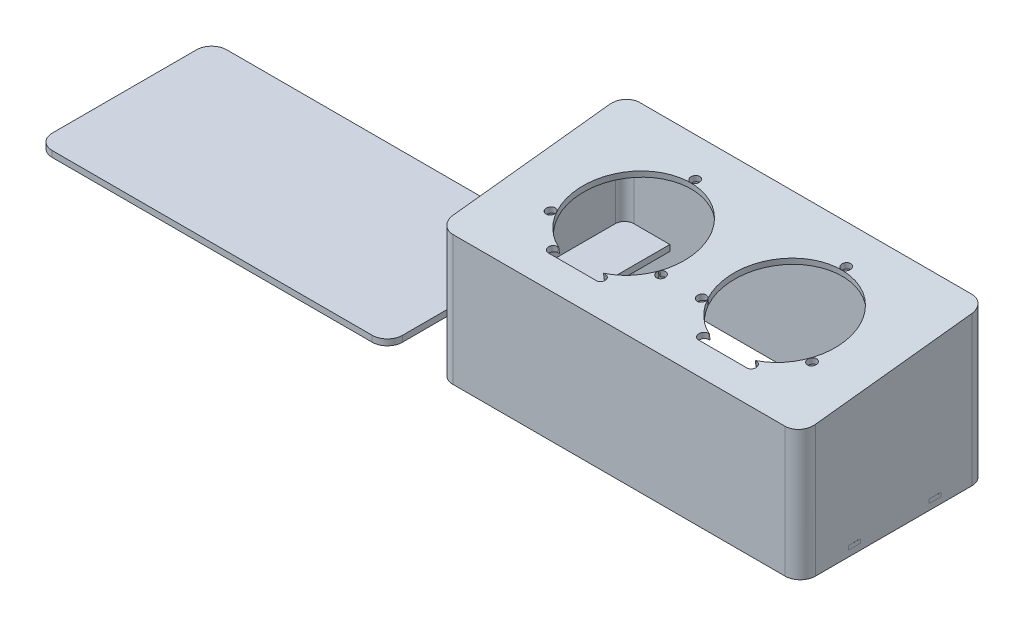
SolidWorks part; units mm, degrees
other "标注1"
sketch "草图11" plane through (-40.2583, 0, -30.485) normal (-0.2386, -0.9638, -0.1194) x (0.9603, -0.2525, 0.1189)
other "标注2"
sketch "草图19" plane through (79.7417, 0, 31.315) normal (0.7607, -0.6049, 0.2355) x (-0.4746, -0.2707, 0.8375)
other "标注3"
sketch "草图27" plane through (-40.2583, 0, -30.485) normal (-0.024, -0.9264, -0.3759) x (0.9235, 0.1235, -0.3633)
ref_plane "前视基准面" through (0, 0, 0) normal (0, 0, 1) x (1, 0, 0)
ref_plane "上视基准面" through (0, 0, 0) normal (0, 1, 0) x (1, 0, 0)
ref_plane "右视基准面" through (0, 0, 0) normal (1, 0, 0) x (0, 0, -1)
other "Configuration Table"
sketch "草图3" plane through (0, 0, 0) normal (0, 1, 0) x (1, 0, 0)
  line L1 (-35.2583, 30.485) -> (74.7417, 30.485)
  line L2 (-40.2583, 25.485) -> (-40.2583, -26.315)
  line L3 (-35.2583, -31.315) -> (74.7417, -31.315)
  line L4 (79.7417, 25.485) -> (79.7417, -26.315)
  arc A0 (-40.2583, -26.315) -> (-35.2583, -31.315) centre (-35.2583, -26.315) ccw
  arc A1 (74.7417, -31.315) -> (79.7417, -26.315) centre (74.7417, -26.315) ccw
  arc A2 (74.7417, 30.485) -> (79.7417, 25.485) centre (74.7417, 25.485) cw
  arc A3 (-35.2583, 30.485) -> (-40.2583, 25.485) centre (-35.2583, 25.485) ccw
  point P6 (-40.2583, -31.315)
  point P11 (79.7417, 30.485)
  point P14 (-40.2583, 30.485)
  dimension "D3" = 5
  dimension "D1" = 61.8
  dimension "D2" = 120
extrude "凸台-拉伸6" add sketch "草图3" along normal blind 50 contours A3 L2 A0 L3 A1 L4 A2 L1
sketch "草图4" plane through (79.7417, 0, 0) normal (1, 0, 0) x (0, 0, -1)
  line L0 (30.485, 50) -> (-31.315, 43)
  line L1 (-31.315, 50) -> (-31.315, 0) construction
  line L2 (-31.315, 43) -> (-31.315, 50)
  line L3 (-31.315, 50) -> (30.485, 50)
  dimension "D1" = 7
extrude "切除-拉伸1" cut sketch "草图4" against normal through all both and the other way through all contours L3 L0 L2
sketch "草图5" plane through (0, 45.9574, 5.2055) normal (0, 0.9936, 0.1125) x (1, 0, 0)
  line L0 (19.7417, -26.2764) -> (19.7417, 35.9188) construction
  line L1 (-35.2583, -26.2764) -> (74.7417, -26.2764) construction
  line L2 (-35.2583, 35.9188) -> (74.7417, 35.9188) construction
  circle A0 centre (44.7417, 3.7236) radius 19
  circle A1 centre (-5.2583, 3.7236) radius 19
  dimension "D1" = 50
  dimension "D2" = 30
extrude "切除-拉伸2" cut sketch "草图5" against normal through all contours A1 | A0
sketch "草图7" plane through (0, 0, 0) normal (0, -1, 0) x (-1, 0, 0)
  line L0 (168.7524, -30.5948) -> (62.7524, -30.5948)
  line L1 (33.2583, -29.315) -> (-72.7417, -29.315)
  line L2 (38.2583, -24.315) -> (38.2583, 23.485)
  line L3 (33.2583, 28.485) -> (-72.7417, 28.485)
  line L4 (-77.7417, -24.315) -> (-77.7417, 23.485)
  line L5 (35.2583, -31.315) -> (-74.7417, -31.315) construction
  line L6 (35.2583, 30.485) -> (-74.7417, 30.485) construction
  line L7 (40.2583, 25.485) -> (40.2583, -26.315) construction
  line L8 (-79.7417, 25.485) -> (-79.7417, -26.315) construction
  line L9 (173.7524, -25.5948) -> (173.7524, 22.2052)
  line L10 (168.7524, 27.2052) -> (62.7524, 27.2052)
  line L11 (57.7524, -25.5948) -> (57.7524, 22.2052)
  arc A0 (173.7524, 22.2052) -> (168.7524, 27.2052) centre (168.7524, 22.2052) ccw
  arc A1 (38.2583, 23.485) -> (33.2583, 28.485) centre (33.2583, 23.485) ccw
  arc A2 (-72.7417, 28.485) -> (-77.7417, 23.485) centre (-72.7417, 23.485) ccw
  arc A3 (-72.7417, -29.315) -> (-77.7417, -24.315) centre (-72.7417, -24.315) cw
  arc A4 (33.2583, -29.315) -> (38.2583, -24.315) centre (33.2583, -24.315) ccw
  arc A5 (62.7524, 27.2052) -> (57.7524, 22.2052) centre (62.7524, 22.2052) ccw
  arc A6 (62.7524, -30.5948) -> (57.7524, -25.5948) centre (62.7524, -25.5948) cw
  arc A7 (168.7524, -30.5948) -> (173.7524, -25.5948) centre (168.7524, -25.5948) ccw
  point P14 (38.2583, 28.485)
  point P19 (-77.7417, -29.315)
  point P22 (38.2583, -29.315)
  dimension "D7" = 5
  dimension "D1" = 116
  dimension "D2" = 57.8
  dimension "D3" = 2
  dimension "D4" = 2
  dimension "D5" = 2
  dimension "D6" = 2
shell "抽壳3" thickness 1.9179 removed face at (44.7417, 0, 15.3741) removed face at (-5.2583, 0, 15.3741) removed face at (-5.2583, 0, 15.3741)
sketch "草图10" plane through (0, 44.0516, 4.9897) normal (0, -0.9936, -0.1125) x (1, 0, 0)
  circle A0 centre (-5.2583, -3.7236) radius 22
  circle A1 centre (-5.2583, -3.7236) radius 19 construction
  circle A2 centre (44.7417, -3.7236) radius 22
  circle A3 centre (44.7417, -3.7236) radius 19 construction
sketch "草图15" plane through (77.8238, 0, 0) normal (-1, 0, 0) x (0, 0, 1)
  line L0 (0, 20) -> (-28.5671, 20)
  line L1 (0, 18) -> (0, 0)
  line L2 (-28.5671, 47.8525) -> (-28.5671, 0) construction
  line L3 (0, 18) -> (-28.5671, 18)
  line L6 (-28.5671, 18) -> (-28.5671, 20)
  line L11 (29.397, 41.287) -> (29.397, 0) construction
  line L12 (0, 18) -> (29.397, 18)
  line L14 (0, 20) -> (29.397, 20)
  line L15 (29.397, 18) -> (29.397, 20)
  line L19 (26.315, 41.6361) -> (-25.485, 47.5034)
  line L20 (26.315, 0) -> (26.315, 41.6361)
  line L21 (-25.485, 0) -> (26.315, 0)
  line L22 (-25.485, 47.5034) -> (-25.485, 0)
  line L23 (26.315, 41.6361) -> (-25.485, 47.5034)
  line L24 (26.315, 0) -> (26.315, 41.6361)
  line L25 (-25.485, 0) -> (26.315, 0)
  line L26 (-25.485, 47.5034) -> (-25.485, 0)
  dimension "D1" = 0
sketch "草图17" plane through (0, 45.9574, 5.2055) normal (0, 0.9936, 0.1125) x (1, 0, 0)
sketch "草图18" plane through (0, 45.9574, 5.2055) normal (0, 0.9936, 0.1125) x (1, 0, 0)
  line L0 (-13.2107, -15.2764) -> (2.7893, -15.2764) construction
  line L1 (-13.2107, -13.7764) -> (2.7893, -13.7764)
  line L2 (-13.2107, -16.7764) -> (2.7893, -16.7764)
  line L3 (36.7178, -15.2764) -> (52.7178, -15.2764) construction
  line L4 (36.7178, -13.6873) -> (52.7178, -13.6873)
  line L5 (36.7178, -16.8655) -> (52.7178, -16.8655)
  arc A0 (-13.2107, -13.7764) -> (-13.2107, -16.7764) centre (-13.2107, -15.2764) ccw
  arc A1 (2.7893, -16.7764) -> (2.7893, -13.7764) centre (2.7893, -15.2764) ccw
  circle A2 centre (-5.2583, 3.7236) radius 19 construction
  arc A3 (36.7178, -13.6873) -> (36.7178, -16.8655) centre (36.7178, -15.2764) ccw
  arc A4 (52.7178, -16.8655) -> (52.7178, -13.6873) centre (52.7178, -15.2764) ccw
  circle A6 centre (44.7417, 3.7236) radius 19 construction
  point P2 (-5.2107, -15.2764)
  point P11 (44.7178, -15.2764)
extrude "切除-拉伸3" cut sketch "草图18" against normal blind 20
sketch "草图20" plane through (0, 45.9574, 5.2055) normal (0, 0.9936, 0.1125) x (1, 0, 0)
  line L0 (19.7417, -26.2764) -> (19.7417, 28.304)
  line L1 (-35.2583, -26.2764) -> (74.7417, -26.2764) construction
  line L2 (-33.2583, 28.304) -> (72.7417, 28.304) construction
  line L3 (-23.5613, -5.5563) -> (-38.2583, -5.5563) construction
  line L4 (-38.2583, -24.1605) -> (-38.2583, 23.3358) construction
  line L5 (-38.2583, -5.5563) -> (77.7417, -5.5563)
  line L6 (77.7417, -24.1605) -> (77.7417, 23.3358) construction
  line L7 (-5.2583, 3.7236) -> (-5.2583, -5.5563)
  line L8 (-5.2583, -5.5563) -> (-5.2583, 28.304)
  circle A5 centre (-5.2617, 24.2356) radius 1.5
  circle A6 centre (-23.5613, -5.5563) radius 1.5
  circle A7 centre (63.0448, -5.5563) radius 1.5
  circle A8 centre (13.0194, -5.5392) radius 1.5
  circle A9 centre (26.464, -5.5392) radius 1.5
  circle A10 centre (44.7451, 24.2356) radius 1.5
extrude "切除-拉伸4" cut sketch "草图20" against normal blind 20 contours A7 | A8 | A6 | A10 | A9 | A5
sketch "草图22" plane through (79.7417, 0, 0) normal (1, 0, 0) x (0, 0, -1)
sketch "草图24" plane through (79.7417, 0, 0) normal (1, 0, 0) x (0, 0, -1)
extrude "凸台-拉伸10" add sketch "草图15" along normal blind 21 contours L6 L0 L14 L15 L12 L3
sketch "草图25" plane through (-40.2583, 0, 0) normal (-1, 0, 0) x (0, 0, 1)
  line L1 (-30.485, 50) -> (-30.485, 0) construction
  line L3 (-30.485, 20) -> (-30.485, 18)
  point P0 (0, 0)
sketch "草图26" plane through (-38.3403, 0, 0) normal (1, 0, 0) x (0, 0, -1)
  line L3 (-29.0671, 16.1759) -> (28.897, 16.1759)
  line L4 (-29.0671, 16.1759) -> (-29.0671, 14.1759)
  line L5 (-29.0671, 14.1759) -> (28.897, 14.1759)
  line L6 (28.897, 16.1759) -> (28.897, 14.1759)
  point P9 (0, 0)
extrude "凸台-拉伸11" add sketch "草图26" along normal blind 15 contours L5 L6 L3 L4
sketch "草图28" plane through (0, 44.0516, 4.9897) normal (0, -0.9936, -0.1125) x (1, 0, 0)
  arc A0 (-21.0475, 22.378) -> (-22.0084, 20.1714) centre (-17.0785, 19.3371) ccw
  arc A1 (-22.0084, -23.8286) -> (-21.1885, -27.5104) centre (-17.0785, -24.6629) ccw
  arc A2 (68.8115, -27.5104) -> (69.0793, -21.4633) centre (72.9215, -24.6629) ccw
  arc A3 (72.8446, 24.3365) -> (77.5831, 21.1454) centre (72.9215, 19.3371) cw
  point P4 (0, 0)
  point P7 (-22.0785, 24.3371)
  point P10 (-22.0785, -29.6629)
  point P15 (77.9215, 24.3371)
  dimension "D3" = 5
  dimension "D1" = 100
  dimension "D2" = 54
extrude "凸台-拉伸12" add sketch "草图7" along normal blind 2 separate body contours L10 A5 L11 A6 L0 A7 L9 A0
sketch "草图29" plane through (-38.3403, 0, 0) normal (1, 0, 0) x (0, 0, -1)
  line L2 (-14.4838, 2) -> (-10.4838, 2)
  line L3 (-10.4838, 2) -> (-10.4838, 3.3101)
  line L4 (-10.4838, 3.3101) -> (-14.4838, 3.3101)
  line L5 (-14.4838, 3.3101) -> (-14.4838, 2)
  line L6 (0, 0) -> (0, 5.8552) construction
  line L7 (14.4838, 3.3101) -> (14.4838, 2)
  line L8 (10.4838, 3.3101) -> (14.4838, 3.3101)
  line L9 (10.4838, 2) -> (10.4838, 3.3101)
  line L10 (14.4838, 2) -> (10.4838, 2)
  dimension "D1" = 4
  dimension "D2" = 1.3101
extrude "凸台-拉伸13" add sketch "草图29" along normal blind 2
sketch "草图30" plane through (-40.2583, 0, 0) normal (-1, 0, 0) x (0, 0, 1)
sketch "草图34" plane through (79.7417, 0, 0) normal (1, 0, 0) x (0, 0, -1)
  line L0 (-15.323, 2) -> (-11.323, 2)
  line L1 (-11.323, 2) -> (-11.323, 3.3101)
  line L2 (-11.323, 3.3101) -> (-15.323, 3.3101)
  line L3 (-15.323, 3.3101) -> (-15.323, 2)
  line L11 (11.323, 2) -> (11.323, 3.3101)
  line L12 (15.323, 3.3101) -> (15.323, 2)
  line L13 (15.323, 2) -> (11.323, 2)
  line L14 (11.323, 3.3101) -> (15.323, 3.3101)
  dimension "D1" = 4
  dimension "D2" = 1.3101
extrude "凸台-拉伸15" add sketch "草图34" along normal blind 0.01 and the other way blind 10 contours L14 L12 L13 L11 | L2 L3 L0 L1
